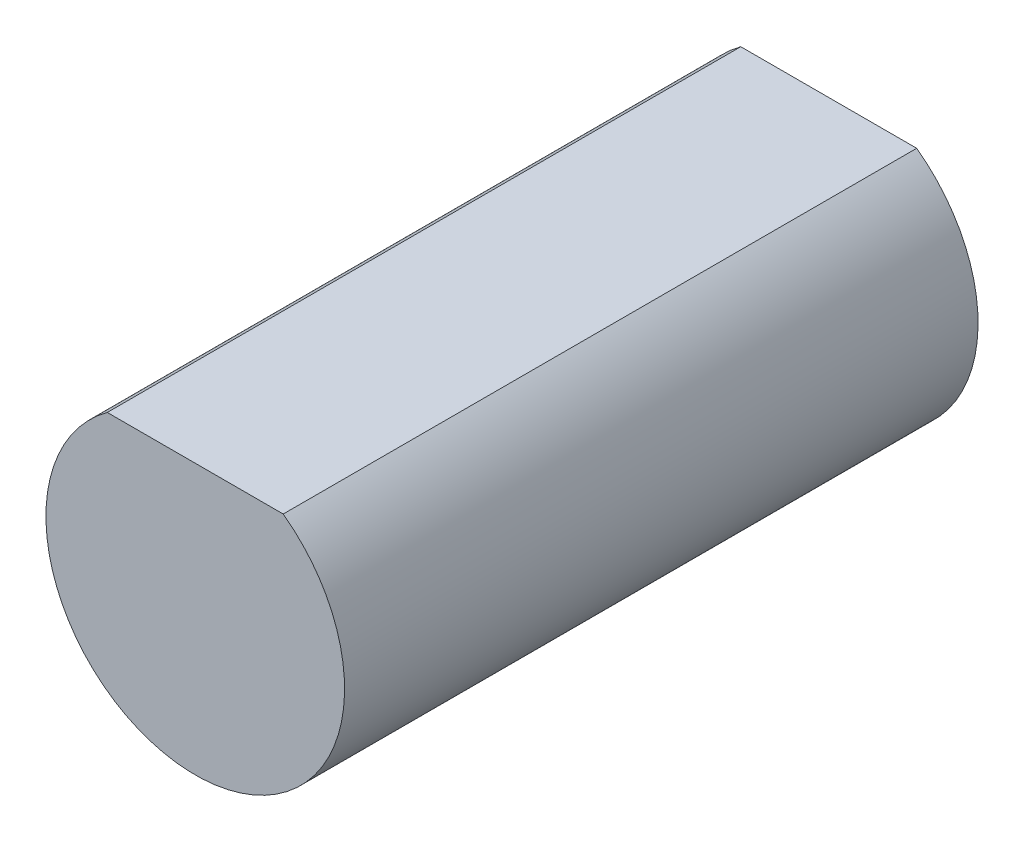
SolidWorks part; units mm, degrees
ref_plane "前视基准面" through (0, 0, 0) normal (0, 0, 1) x (1, 0, 0)
ref_plane "上视基准面" through (0, 0, 0) normal (0, 1, 0) x (1, 0, 0)
ref_plane "右视基准面" through (0, 0, 0) normal (1, 0, 0) x (0, 0, -1)
other "Configuration Table"
sketch "草图1" plane through (0, 0, 0) normal (0, 0, 1) x (1, 0, 0)
  circle A0 centre (0, 0) radius 9.9
  dimension "D1" = 19.8
extrude "凸台-拉伸1" add sketch "草图1" along normal blind 42
sketch "草图2" plane through (0, 0, 42) normal (0, 0, 1) x (1, 0, 0)
  line L0 (-6, 8) -> (6, 8)
  arc A0 (6, 8) -> (-6, 8) centre (0, 0) ccw
  dimension "D1" = 20
  dimension "D2" = 8
extrude "切除-拉伸1" cut sketch "草图2" against normal through all
